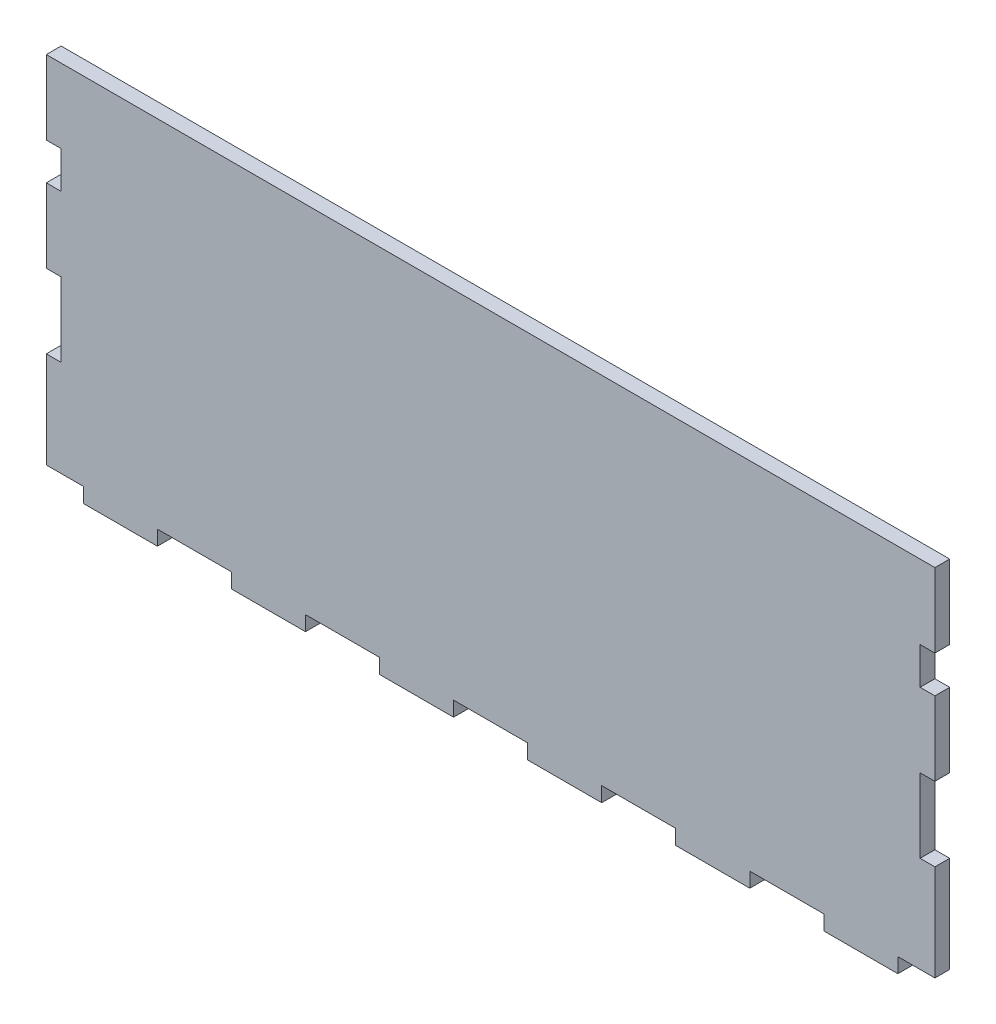
SolidWorks part; units mm, degrees
ref_plane "Front Plane" through (0, 0, 0) normal (0, 0, 1) x (1, 0, 0)
ref_plane "Top Plane" through (0, 0, 0) normal (0, 1, 0) x (1, 0, 0)
ref_plane "Right Plane" through (0, 0, 0) normal (1, 0, 0) x (0, 0, -1)
sketch "Sketch1" plane through (0, 0, 0) normal (0, 0, 1) x (1, 0, 0)
  line L0 (0, 0) -> (0, -127) construction
  line L1 (152.4, 0) -> (-152.4, 0)
  line L2 (12.7, -127) -> (-12.7, -127)
  line L3 (-12.7, -127) -> (-12.7, -121.92)
  line L4 (-12.7, -121.92) -> (-38.1, -121.92)
  line L5 (-38.1, -121.92) -> (-38.1, -127)
  line L6 (-38.1, -127) -> (-63.5, -127)
  line L7 (-63.5, -127) -> (-63.5, -121.92)
  line L8 (-63.5, -121.92) -> (-88.9, -121.92)
  line L9 (-88.9, -121.92) -> (-88.9, -127)
  line L10 (-88.9, -127) -> (-114.3, -127)
  line L11 (-152.4, -127) -> (-152.4, -114.3)
  line L12 (-114.3, -127) -> (-114.3, -121.92)
  line L13 (-114.3, -121.92) -> (-139.7, -121.92)
  line L14 (-139.7, -121.92) -> (-139.7, -127)
  line L15 (-139.7, -127) -> (-152.4, -127)
  line L16 (-152.4, -114.3) -> (-147.32, -114.3)
  line L17 (-147.32, -114.3) -> (-147.32, -88.9)
  line L18 (-147.32, -88.9) -> (-152.4, -88.9)
  line L19 (-152.4, -63.5) -> (-147.32, -63.5)
  line L20 (-147.32, -63.5) -> (-147.32, -38.1)
  line L21 (-147.32, -38.1) -> (-152.4, -38.1)
  line L22 (-152.4, -25.4) -> (-147.32, -25.4)
  line L23 (-147.32, -25.4) -> (-147.32, 0)
  line L24 (-152.4, -88.9) -> (-152.4, -63.5)
  line L25 (-152.4, -38.1) -> (-152.4, -25.4)
  line L26 (152.4, -38.1) -> (152.4, -25.4)
  line L27 (152.4, -88.9) -> (152.4, -63.5)
  line L28 (147.32, -25.4) -> (147.32, 0)
  line L29 (152.4, -25.4) -> (147.32, -25.4)
  line L30 (147.32, -38.1) -> (152.4, -38.1)
  line L31 (147.32, -63.5) -> (147.32, -38.1)
  line L32 (152.4, -63.5) -> (147.32, -63.5)
  line L33 (147.32, -88.9) -> (152.4, -88.9)
  line L34 (147.32, -114.3) -> (147.32, -88.9)
  line L35 (152.4, -114.3) -> (147.32, -114.3)
  line L36 (139.7, -127) -> (152.4, -127)
  line L37 (139.7, -121.92) -> (139.7, -127)
  line L38 (114.3, -121.92) -> (139.7, -121.92)
  line L39 (114.3, -127) -> (114.3, -121.92)
  line L40 (152.4, -127) -> (152.4, -114.3)
  line L41 (88.9, -127) -> (114.3, -127)
  line L42 (88.9, -121.92) -> (88.9, -127)
  line L43 (63.5, -121.92) -> (88.9, -121.92)
  line L44 (63.5, -127) -> (63.5, -121.92)
  line L45 (38.1, -127) -> (63.5, -127)
  line L46 (38.1, -121.92) -> (38.1, -127)
  line L47 (12.7, -121.92) -> (38.1, -121.92)
  line L48 (12.7, -127) -> (12.7, -121.92)
  line L49 (-147.32, 0) -> (147.32, 0)
  line L50 (-152.4, 0) -> (-152.4, -127)
  line L51 (-152.4, -127) -> (152.4, -127)
  line L52 (152.4, -127) -> (152.4, 0)
  line L53 (-147.32, 0) -> (-147.32, -114.3)
  line L54 (-139.7, -121.92) -> (139.7, -121.92)
  line L55 (147.32, 0) -> (147.32, -114.3)
  line L56 (-139.7, -121.92) -> (-152.4, -121.92)
  line L57 (139.7, -121.92) -> (152.4, -121.92)
  dimension "D1" = 152.4
  dimension "D2" = 127
  dimension "D3" = 12.7
  dimension "D4" = 25.4
  dimension "D5" = 5.08
  dimension "D6" = 12.7
  dimension "D7" = 25.4
extrude "Boss-Extrude1" add sketch "Sketch1" along normal mid plane 5.08 contours L1 L50 L22 L23 | L21 L50 L19 L20 | L18 L50 L16 L17 | L14 L51 L12 L13 | L9 L51 L7 L8 | L0 L49 L23 L53 L20 L17 L16 L11 L15 L14 L13 L54 L8 L4 | L1 L0 L54 L47 L43 L38 L37 L36 L40 L35 L34 L55 L31 L28 | L5 L51 L3 L4 | L44 L51 L42 L43 | L48 L51 L46 L47 | L39 L51 L37 L38 | L35 L52 L33 L34 | L32 L52 L30 L31 | L29 L52 L1 L28 region at (73.8239, -61.0829, 0) region at (-73.8239, -61.0829, 0) region at (149.86, -12.7, 0) region at (-149.86, -12.7, 0) region at (-25.4, -124.46, 0) region at (25.4, -124.46, 0) region at (149.86, -50.8, 0) region at (-149.86, -50.8, 0) region at (-76.2, -124.46, 0) region at (76.2, -124.46, 0) region at (149.86, -101.6, 0) region at (-149.86, -101.6, 0) region at (-127, -124.46, 0) region at (127, -124.46, 0)
